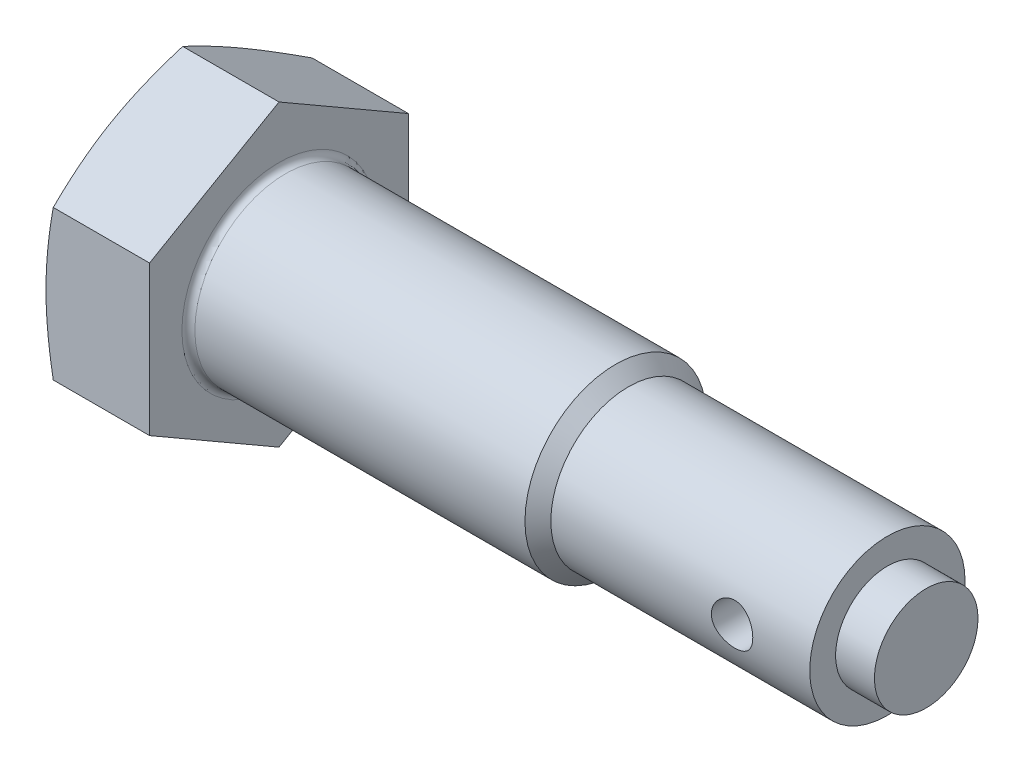
SolidWorks part; units mm, degrees
ref_plane "Front" through (0, 0, 0) normal (0, 0, 1) x (1, 0, 0)
ref_plane "Top" through (0, 0, 0) normal (0, 1, 0) x (1, 0, 0)
ref_plane "Right" through (0, 0, 0) normal (1, 0, 0) x (0, 0, -1)
sketch "Sketch1" plane through (0, 0, 0) normal (1, 0, 0) x (0, 0, -1)
  line L1 (0, -5.7735) -> (5, -2.8868)
  line L2 (5, -2.8868) -> (5, 2.8868)
  line L3 (5, 2.8868) -> (0, 5.7735)
  line L4 (0, 5.7735) -> (-5, 2.8868)
  line L5 (-5, 2.8868) -> (-5, -2.8868)
  line L6 (-5, -2.8868) -> (0, -5.7735)
  circle A0 centre (0, 0) radius 5 construction
extrude "BaseHead" add sketch "Sketch1" along normal blind 4
sketch "Sketch2" plane through (4, 0, 0) normal (1, 0, 0) x (0, 0, -1)
  circle A0 centre (0, 0) radius 3.5
extrude "Basebody1" add sketch "Sketch2" along normal blind 13
sketch "Sketch4" plane through (17, 0, 0) normal (1, 0, 0) x (0, 0, -1)
  circle A0 centre (0, 0) radius 3
extrude "Basebody2" add sketch "Sketch4" along normal offset from surface (12 mm away) 25 up to face at (4, 0, 0) offset beyond the face yes
cosmetic thread "ThreadCosmetic1" [suppressed] parameters "dn"=4.5
sketch "Sketch5" plane through (29, 0, 0) normal (1, 0, 0) x (0, 0, -1)
  circle A0 centre (0, 0) radius 2
  dimension "dp" = 4
extrude "Cut-Extrude1" cut sketch "Sketch5" against normal blind 1.5 flip side to cut
sketch "Sketch6" plane through (0, 0, 0) normal (0, 0, 1) x (1, 0, 0)
  line L0 (0, 5.7735) -> (0.2815, 5.7735)
  line L1 (0.2815, 5.7735) -> (0, 5)
  line L3 (0, 5) -> (0, 5.7735)
  line L4 (-1.5773, 0) -> (3.1205, 0) construction
  line L6 (4, 5.7735) -> (0, 5.7735) construction
  dimension "D1" = 20
  dimension "D2" = 10
revolve "HeadChamfer" cut sketch "Sketch6" angle 360 about L4
fillet "HeadFillet" radius 0.25 1 edges at (4, 0, 3.5)
chamfer "Chamfer1" distance 0.5 angle 45 1 edges at (17, 0, -3)
sketch "Sketch7" plane through (0, 0, 0) normal (0, 0, 1) x (1, 0, 0)
  line L1 (4, 5.7735) -> (4, 2.8868) construction
  line L4 (27.5, 0) -> (17.5, 0) construction
  circle A0 centre (24.5, 0) radius 0.8
  dimension "d1" = 1.6
  dimension "lh" = 20.5
extrude "Hole" cut sketch "Sketch7" against normal through all and the other way through all
sketch "Sketch8" plane through (0, 0, 0) normal (0, 0, 1) x (1, 0, 0)
  line L0 (27.125, 3.2) -> (27.875, 3.2)
  line L1 (27.875, 3.2) -> (27.875, 3)
  line L2 (27.875, 3) -> (27.5, 2.3505)
  line L3 (27.125, 3) -> (27.5, 2.3505)
  line L4 (27.125, 3.2) -> (27.125, 3)
  line L5 (27.4981, 0) -> (0, 0) construction
  line L6 (27.125, 3) -> (27.875, 3) construction
  line L7 (27.5, 3) -> (27.5, 2.3505) construction
  line L8 (27.5, -3) -> (27.5, 3) construction
  line L9 (27.5, 3) -> (17.5, 3) construction
  point P5 (27.5, 3.2)
  dimension "D1" = 0.2
  dimension "D2" = 0.75
revolve "Cut-Revolve10" [suppressed] cut sketch "Sketch8" angle 360 about L5
pattern_linear "LPattern10" [suppressed] count 12 spacing 0.9 along (-1, 0, 0) of bodies 107
equation "\"D1@Chamfer1\" =  ( \"ds@Sketch2\" - \"d@Sketch4\" )  / 2"
equation "\"D2@Sketch6\" = \"s@Sketch1\""
equation "\"D2@Sketch8\" =  ( \"d@Sketch4\" - \"dn@ThreadCosmetic1\" )  / 2"
equation "\"D3@LPattern10\" = \"D2@Sketch8\" * 1.2"
equation "\"D1@LPattern10\" = (  \"l@Basebody2\"  - \"l3@Basebody1\" -\"l2@Cut-Extrude1\" )  / \"D3@LPattern10\""
